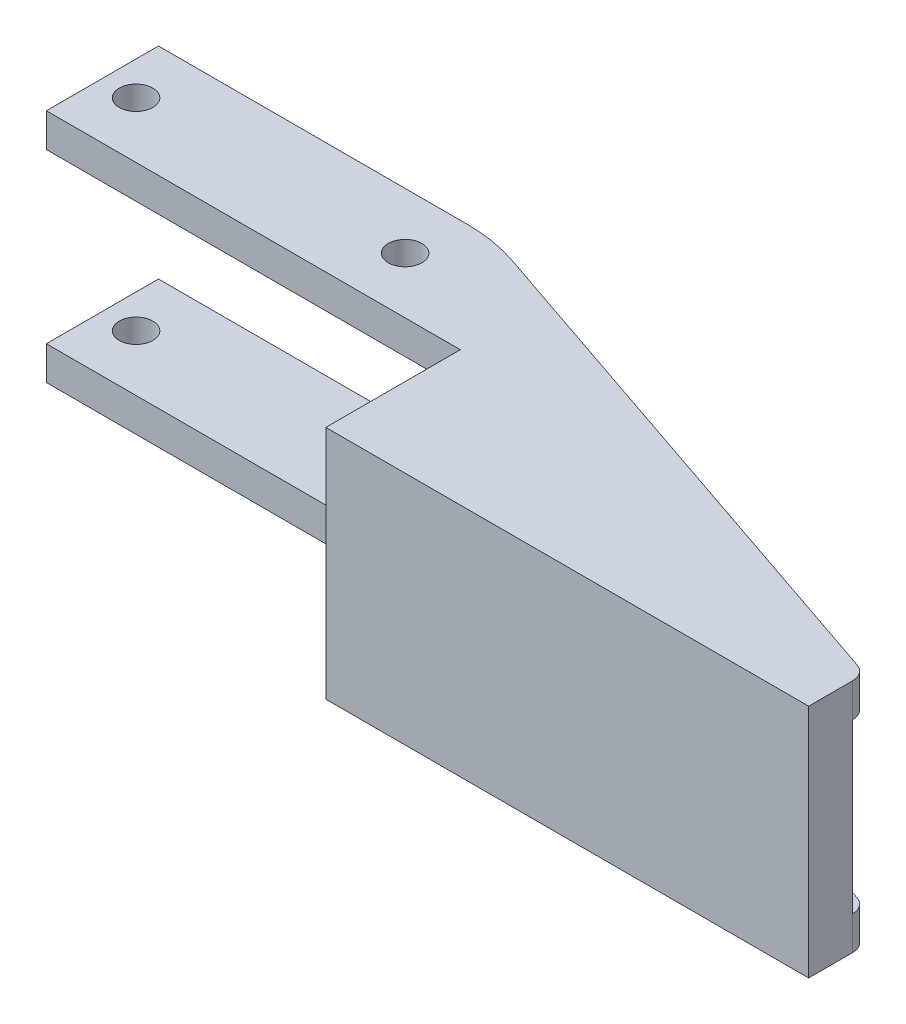
SolidWorks part; units mm, degrees
material "ABS"
ref_plane "Front Plane" through (0, 0, 0) normal (0, 0, 1) x (1, 0, 0)
ref_plane "Top Plane" through (0, 0, 0) normal (0, 1, 0) x (1, 0, 0)
ref_plane "Right Plane" through (0, 0, 0) normal (1, 0, 0) x (0, 0, -1)
sketch "Sketch1" plane through (0, 0, 0) normal (0, 1, 0) x (1, 0, 0)
  line L0 (-4.5779, 9.3563) -> (42.0567, -6.4995)
  line L1 (-36.9262, 10.1547) -> (-9.4065, 10.1547)
  line L2 (-36.9262, 10.1547) -> (-36.9262, 0.1547)
  line L3 (0, -11.8453) -> (43.0738, -11.8453)
  line L4 (43.0738, -7.9196) -> (43.0738, -11.8453)
  line L5 (-36.9262, 10.1547) -> (43.0738, -11.8453) construction
  line L6 (-3.5929, 0.1547) -> (26.2671, -1.131) construction
  line L10 (-36.9262, 0.1547) -> (0, 0.1547)
  line L11 (0, -11.8453) -> (0, 0.1547)
  arc A0 (-9.4065, 10.1547) -> (-4.5779, 9.3563) centre (-9.4065, -4.8453) cw
  arc A1 (42.0567, -6.4995) -> (43.0738, -7.9196) centre (41.5738, -7.9196) cw
  point P0 (0, 0)
  point P10 (-6.9262, 10.1547)
  point P13 (43.0738, -6.8453)
  dimension "D6" = 15
  dimension "D7" = 1.5
  dimension "D1" = 10
  dimension "D2" = 80
  dimension "D3" = 5
  dimension "D4" = 50
  dimension "D5" = 10.7143
  dimension "D8" = 12
  dimension "D9" = 33.3333
extrude "Boss-Extrude1" add sketch "Sketch1" against normal blind 3
extrude "Boss-Extrude2" add sketch "Sketch1<2>" along normal blind 3 from offset 15 separate body
sketch "Sketch1<2>" plane through (0, 0, 0) normal (0, 1, 0) x (1, 0, 0) same geometry as "Sketch1"
hole_wizard "Ø3.0mm Clearance Dowel Hole1" positions "Sketch2" profile "Sketch3" hole size "Ø3.0" standard "ANSI Metric" end condition through all
sketch "Sketch2" plane through (0, -3, 0) normal (0, -1, 0) x (-1, 0, 0)
  line L0 (36.9262, 10.1547) -> (36.9262, 0.1547) construction
  point P0 (33.9262, 5.1547)
  point P2 (9.9262, 5.1547)
  point P7 (36.9262, 5.1547)
  dimension "D1" = 3
  dimension "D2" = 24
sketch "Sketch3" plane through (-33.9262, -3, -5.1547) normal (1, 0, 0) x (0, 0, -1)
  line L0 (0, 0) -> (0, 21)
  line L1 (0, 21) -> (1.5, 21)
  line L2 (1.5, 21) -> (1.5, 0)
  line L5 (1.5, 0) -> (0, 0)
  line L11 (0, -6.35) -> (0, 107.95) construction
  dimension "Thru Hole Dia." = 3
  dimension "Thru Hole Depth" = 21
sketch "Sketch5" plane through (0, 0, 0) normal (0, 1, 0) x (1, 0, 0)
  line L1 (0, -11.8453) -> (43.0738, -11.8453)
  line L2 (0, -11.8453) -> (0, -7.9196)
  line L3 (0, -7.9196) -> (43.0738, -7.9196)
  line L4 (43.0738, -11.8453) -> (43.0738, -7.9196)
extrude "Boss-Extrude3" add sketch "Sketch5" along normal up to surface (15 mm away) up to face at (-33.9262, 15, -6.6547)
